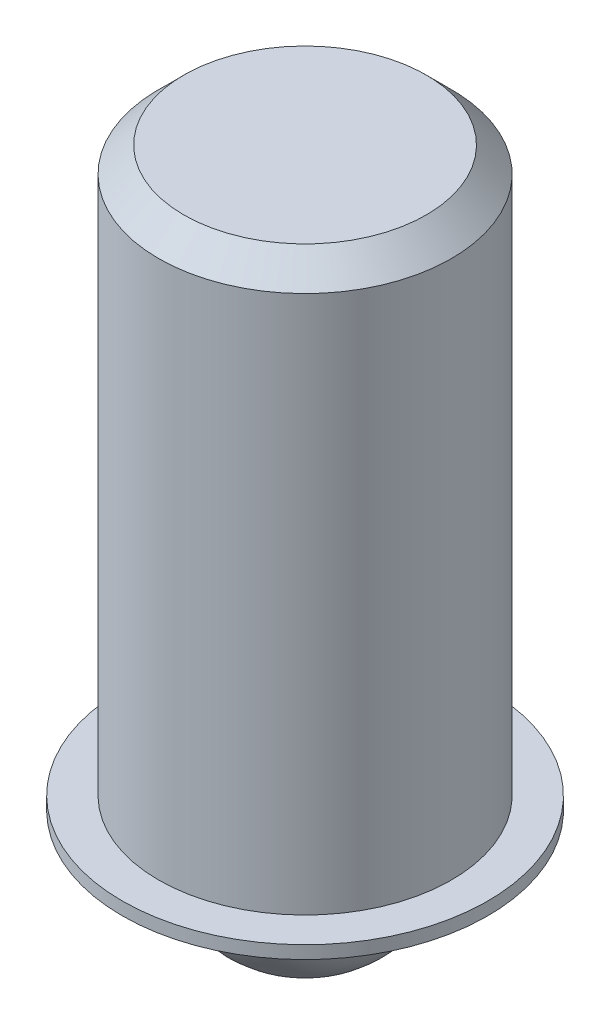
SolidWorks part; units mm, degrees
material "Plain Carbon Steel"
ref_plane "Front" through (0, 0, 0) normal (0, 0, 1) x (1, 0, 0)
ref_plane "Top" through (0, 0, 0) normal (0, 1, 0) x (1, 0, 0)
ref_plane "Right" through (0, 0, 0) normal (1, 0, 0) x (0, 0, -1)
sketch "Sketch24" plane through (0, 0, 0) normal (1, 0, 0) x (0, 0, -1)
  line L5 (0, 7.5565) -> (0, -7.5565) construction
  line L6 (-2.3749, -5.9382) -> (-2.3749, -4.6609) construction
  line L7 (-2.3749, -5.9382) -> (-3.9624, -4.9403) construction
  line L8 (-3.9624, -4.9403) -> (-3.9624, -4.6609)
  line L9 (-3.9624, -4.6609) -> (-3.175, -4.6609)
  line L10 (-3.175, -4.6609) -> (-3.175, 7.0104)
  line L11 (-3.175, 7.0104) -> (-2.6289, 7.5565)
  line L12 (-2.6289, 7.5565) -> (0, 7.5565)
  line L13 (0, -7.5565) -> (0, 7.5565) construction
  line L14 (-3.9624, -4.9403) -> (-2.6289, -5.7785)
  line L15 (-2.6289, -5.7785) -> (-2.6289, -4.6609) construction
  line L16 (-2.6289, -5.7785) -> (-2.3749, -5.7785)
  line L17 (-2.6289, -4.6609) -> (0, -4.6609) construction
  line L18 (0, -4.6609) -> (0, 7.5565)
  line L19 (-2.3749, -5.7785) -> (-2.3749, -4.6609)
  line L20 (-2.3749, -4.6609) -> (0, -4.6609)
  circle A1 centre (0, -5.1816) radius 2.3749 construction
  dimension "Ball Dia" = 4.7498
  dimension "Flange Dia" = 7.9248
  dimension "Body Lg" = 12.2174
  dimension "Body Dia" = 6.35
  dimension "D1" = 0.2794
  dimension "D2" = 45
  dimension "Flange Lg" = 1.1176
  dimension "Ball Projection" = 1.778
  dimension "D3" = 0.254
revolve "Revolve2" add sketch "Sketch24" angle 360 about L5
sketch "Sketch25" plane through (0, 0, 0) normal (1, 0, 0) x (0, 0, -1)
  line L0 (0, -7.5565) -> (0, -2.8067)
  circle A0 centre (0, -5.1816) radius 2.3749 construction
  arc A2 (0, -7.5565) -> (0, -2.8067) centre (0, -5.1816) cw
revolve "Revolve3" add sketch "Sketch25" angle 360 about L18
ref_axis "Center Axis 1" through (0, 19.1529, 0) along (0, -1, 0)
ref_plane "Contact Plane 1" through (0, -4.6609, 0) normal (0, 1, 0) x (1, 0, 0)
equation "\"D1@Sketch24\" = \"Flange Lg@Sketch24\"/4"
